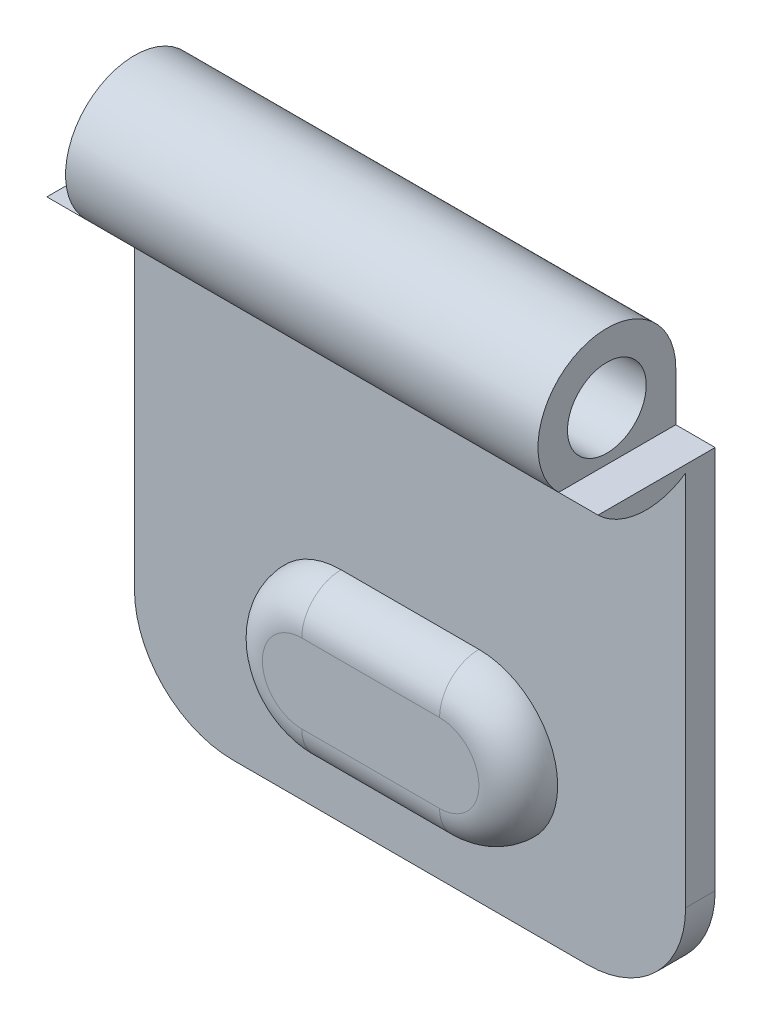
SolidWorks part; units mm, degrees
ref_plane "Front Plane" through (0, 0, 0) normal (0, 0, 1) x (1, 0, 0)
ref_plane "Top Plane" through (0, 0, 0) normal (0, 1, 0) x (1, 0, 0)
ref_plane "Right Plane" through (0, 0, 0) normal (1, 0, 0) x (0, 0, -1)
sketch "Sketch1" plane through (0, 0, 0) normal (1, 0, 0) x (0, 0, -1)
  line L2 (3.5, 0) -> (3.5, -27)
  line L3 (3.5, -27) -> (2, -27)
  line L4 (2, -2.8723) -> (2, -27)
  circle A0 centre (0, 0) radius 2
  arc A1 (3.5, 0) -> (2, -2.8723) centre (0, 0) ccw
  circle A3 centre (0, 0) radius 3.5 construction
  point P8 (3.5, 0)
  dimension "D1" = 4
  dimension "D3" = 1.5
  dimension "D4" = 27
  dimension "D2" = 1.5
extrude "Boss-Extrude1" add sketch "Sketch1" along normal blind 14 and the other way blind 14
fillet "Fillet1" radius 5 2 edges at (-14, -27, -2.75) (14, -27, -2.75)
sketch "Sketch2" plane through (0, 0, -2) normal (0, 0, 1) x (1, 0, 0)
  line L0 (0, -27) -> (0, -19.8812) construction
  line L1 (-9, -27) -> (9, -27) construction
  line L2 (-3.5, -19.8812) -> (3.5, -19.8812) construction
  line L3 (-3.5, -15.8812) -> (3.5, -15.8812)
  line L4 (-3.5, -23.8812) -> (3.5, -23.8812)
  arc A0 (-3.5, -15.8812) -> (-3.5, -23.8812) centre (-3.5, -19.8812) ccw
  arc A1 (3.5, -23.8812) -> (3.5, -15.8812) centre (3.5, -19.8812) ccw
  point P7 (0, -19.8812)
extrude "Boss-Extrude2" add sketch "Sketch2" along normal blind 2
fillet "Fillet2" radius 2 4 edges at (-7.5, -19.8812, 0) (0, -15.8812, 0) (7.5, -19.8812, 0) (0, -23.8812, 0)
sketch "Sketch3" plane through (0, 0, -3.5) normal (0, 0, -1) x (-1, 0, 0)
  line L0 (0, -17.8812) -> (0, -21.8812) construction
  line L1 (-3.5, -17.8812) -> (3.5, -17.8812) construction
  line L2 (3.5, -21.8812) -> (-3.5, -21.8812) construction
  line L3 (-4, -19.9377) -> (4, -19.9377) construction
  line L4 (-4, -17.4377) -> (4, -17.4377)
  line L5 (-4, -22.4377) -> (4, -22.4377)
  arc A0 (-4, -17.4377) -> (-4, -22.4377) centre (-4, -19.9377) ccw
  arc A1 (4, -22.4377) -> (4, -17.4377) centre (4, -19.9377) ccw
  point P8 (0, -19.9377)
extrude "Cut-Extrude1" cut sketch "Sketch3" against normal blind 2
fillet "Fillet3" radius 2 4 edges at (-6.5, -19.9377, -1.5) (0, -22.4377, -1.5) (6.5, -19.9377, -1.5) (0, -17.4377, -1.5)
fillet "Fillet4" radius 2 4 edges at (-6.5, -19.9377, -3.5) (0, -22.4377, -3.5) (6.5, -19.9377, -3.5) (0, -17.4377, -3.5)
sketch "Sketch4" plane through (0, 0, -3.5) normal (0, 0, -1) x (-1, 0, 0)
  line L1 (-14, 3.5) -> (-12, 3.5)
  line L2 (-14, 3.5) -> (-14, -2.5)
  line L3 (-14, -2.5) -> (-12, -2.5)
  line L4 (-12, 3.5) -> (-12, -2.5)
  line L5 (14, 3.5) -> (12, 3.5)
  line L6 (14, 3.5) -> (14, -2.5)
  line L7 (14, -2.5) -> (12, -2.5)
  line L8 (12, 3.5) -> (12, -2.5)
  dimension "D1" = 12
  dimension "D2" = 12
  dimension "D3" = 6
  dimension "D4" = 6
extrude "Cut-Extrude2" cut sketch "Sketch4" against normal through all
